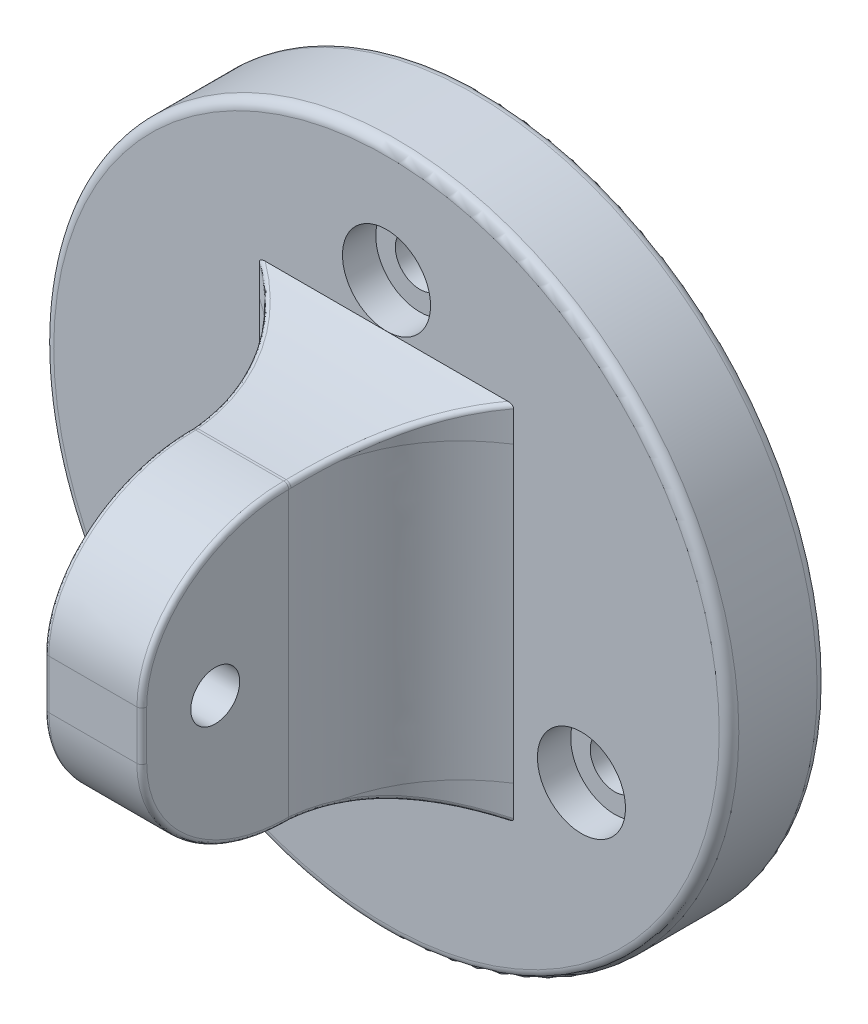
SolidWorks part; units mm, degrees
ref_plane "Ebene vorne" through (0, 0, 0) normal (0, 0, 1) x (1, 0, 0)
ref_plane "Ebene oben" through (0, 0, 0) normal (0, 1, 0) x (1, 0, 0)
ref_plane "Ebene rechts" through (0, 0, 0) normal (1, 0, 0) x (0, 0, -1)
ref_plane "Ebene1" through (0, 0, 10) normal (0, 0, 1) x (1, 0, 0)
ref_plane "Ebene2" through (0, 10, 0) normal (0, 1, 0) x (1, 0, 0)
ref_plane "Ebene3" through (10, 0, 0) normal (1, 0, 0) x (0, 0, -1)
sketch "Skizze1" plane through (0, 0, 10) normal (0, 0, 1) x (1, 0, 0)
  line L0 (55, 10) -> (-55, 10) construction
  line L1 (10, -88.99) -> (10, 88.99) construction
  circle A0 centre (10, 10) radius 35
  circle A1 centre (10, 33) radius 2.5
  circle A2 centre (29.9186, -1.5) radius 2.5
  circle A3 centre (-9.9186, -1.5) radius 2.5
  point P15 (10, 10)
  dimension "D1" = 23
  dimension "D2" = 70
  dimension "D3" = 5
  dimension "D4" = 3
extrude "Aufsatz-Linear austragen1" add sketch "Skizze1" against normal blind 10
sketch "Skizze2" plane through (0, 0, 10) normal (0, 0, 1) x (1, 0, 0)
  line L0 (10, -88.99) -> (10, 88.99) construction
  line L1 (5, 25) -> (15, 25)
  line L2 (5, 25) -> (5, -5)
  line L3 (5, -5) -> (15, -5)
  line L4 (15, 25) -> (15, -5)
  line L5 (55, 10) -> (-55, 10) construction
  dimension "D1" = 10
  dimension "D2" = 30
  dimension "D3" = 5
  dimension "D4" = 15
extrude "Aufsatz-Linear austragen2" add sketch "Skizze2" along normal blind 30
ref_plane "Ebene4" through (0, 25, 0) normal (0, 1, 0) x (1, 0, 0)
sketch "Skizze4" plane through (0, 25, 0) normal (0, 1, 0) x (1, 0, 0)
  line L0 (5, -10) -> (5, -25)
  line L1 (5, -40) -> (5, -10) construction
  line L2 (5, -10) -> (-3, -10)
  line L3 (10, -88.99) -> (10, 88.99) construction
  line L4 (15, -10) -> (23, -10)
  line L5 (15, -10) -> (15, -25)
  spline S0 degree 2 poles (-3, -10) (4.7086, -14.9989) (5, -25) knots 0 0 0 1 1 1
  spline S1 degree 2 poles (23, -10) (15.2914, -14.9989) (15, -25) knots 0 0 0 1 1 1
  point P5 (1, -13.5)
  dimension "D1" = 4
  dimension "D2" = 3.5
  dimension "D3" = 8
extrude "Aufsatz-Linear austragen3" add sketch "Skizze4" against normal blind 30
sketch "Skizze5" plane through (10, 0, 0) normal (1, 0, 0) x (0, 0, -1)
  line L0 (-9.9872, 25) -> (-9.9872, 28.5)
  line L1 (-9.9872, 25) -> (-24.9872, 25)
  line L2 (-10, 25) -> (-25, 25) construction
  line L7 (55, 10) -> (-55, 10) construction
  line L8 (-9.9872, -5) -> (-24.9872, -5)
  line L9 (-9.9872, -5) -> (-9.9872, -8.5)
  spline S0 degree 2 poles (-9.9872, 28.5) (-17.0144, 25.4674) (-24.7548, 25) knots 0 0 0 1 1 1
  spline S1 degree 2 poles (-9.9872, -8.5) (-17.0144, -5.4674) (-24.7548, -5) knots 0 0 0 1 1 1
  point P2 (-13.9872, 27)
  point P4 (-17.4872, 25)
  dimension "D1" = 4
  dimension "D2" = 3.5
  dimension "D3" = 2
extrude "Aufsatz-Linear austragen5" add sketch "Skizze5" along normal blind 13 and the other way blind 13 contours S1 L9 L8 | L0 S0 L1 region at (10, 26.0516, 14.0682) region at (10, -6.0516, 14.0682)
sketch "Skizze8" plane through (0, -5, 0) normal (0, 1, 0) x (1, 0, 0)
  line L2 (-3, -24.7548) -> (4.9917, -24.7548)
  line L3 (-3, -10) -> (-3, -24.7548)
  line L4 (-3, -24.7548) -> (4.9917, -24.7548)
  line L5 (-3, -10) -> (-3, -24.7548)
  parabola Q1 (4.9917, -24.7548) -> (-3, -10) focus (-4.6258, -19.2941) apex (1.9985, -14.8266)
  parabola Q2 (4.9917, -24.7548) -> (-3, -10) focus (-4.6258, -19.2941) apex (1.9985, -14.8266)
  dimension "D1" = 0
extrude "Schnitt-Linear austragen2" cut sketch "Skizze8" against normal blind 15
sketch "Skizze9" plane through (0, -5, 0) normal (0, 1, 0) x (1, 0, 0)
  line L2 (23, -24.7548) -> (23, -10)
  line L3 (15.0083, -24.7548) -> (23, -24.7548)
  line L4 (23, -24.7548) -> (23, -10)
  line L5 (15.0083, -24.7548) -> (23, -24.7548)
  parabola Q1 (23, -10) -> (15.0083, -24.7548) focus (24.6258, -19.2941) apex (18.0015, -14.8266)
  parabola Q2 (23, -10) -> (15.0083, -24.7548) focus (24.6258, -19.2941) apex (18.0015, -14.8266)
  dimension "D1" = 0
extrude "Schnitt-Linear austragen3" cut sketch "Skizze9" against normal blind 15
sketch "Skizze10" plane through (0, 25, 0) normal (0, -1, 0) x (1, 0, 0)
  line L0 (4.9917, 24.7548) -> (-3, 24.7548) construction
  line L1 (-3, 24.7548) -> (-3, 10) construction
  line L2 (23, 10) -> (23, 24.7548) construction
  line L3 (23, 24.7548) -> (15.0083, 24.7548) construction
  line L4 (4.9917, 24.7548) -> (-3, 24.7548)
  line L5 (-3, 24.7548) -> (-3, 10)
  line L6 (23, 10) -> (23, 24.7548)
  line L7 (23, 24.7548) -> (15.0083, 24.7548)
  parabola Q0 (-3, 10) -> (4.9917, 24.7548) focus (-4.6258, 19.2941) apex (1.9985, 14.8266) construction
  parabola Q1 (15.0083, 24.7548) -> (23, 10) focus (24.6258, 19.2941) apex (18.0015, 14.8266) construction
  parabola Q2 (-3, 10) -> (4.9917, 24.7548) focus (-4.6258, 19.2941) apex (1.9985, 14.8266)
  parabola Q3 (15.0083, 24.7548) -> (23, 10) focus (24.6258, 19.2941) apex (18.0015, 14.8266)
extrude "Schnitt-Linear austragen4" cut sketch "Skizze10" against normal blind 15
sketch "Skizze11" plane through (0, 0, 10) normal (0, 0, 1) x (1, 0, 0)
  circle A0 centre (-9.9186, -1.5) radius 4.5
  circle A1 centre (29.9186, -1.5) radius 4.5
  circle A2 centre (10, 33) radius 4.5
extrude "Schnitt-Linear austragen5" cut sketch "Skizze11" against normal blind 3.4
fillet "Verrundung4" radius 15 2 edges at (10, -5, 40) (10, 25, 40) second distance 12.5 first distance on face at (9.9986, -5, 29.9183) first distance on face at (9.9986, 25, 29.9183)
fillet "Verrundung5" radius 1 2 edges at (45, 10, 0) (45, 10, 10)
fillet "Verrundung7" radius 0.5 8 edges at (2.4028, -6.5581, 15.4576) (18.5972, -6.9955, 14.0013)
sketch "Skizze12" plane through (5, 0, 0) normal (-1, 0, 0) x (0, 0, 1)
  line L0 (40, 12.5) -> (40, 7.5) construction
  line L1 (25, 25) -> (24.7548, 25) construction
  circle A0 centre (32.5, 10) radius 2.5
  dimension "D1" = 7.5
  dimension "D2" = 15
extrude "Schnitt-Linear austragen6" cut sketch "Skizze12" against normal blind 30
